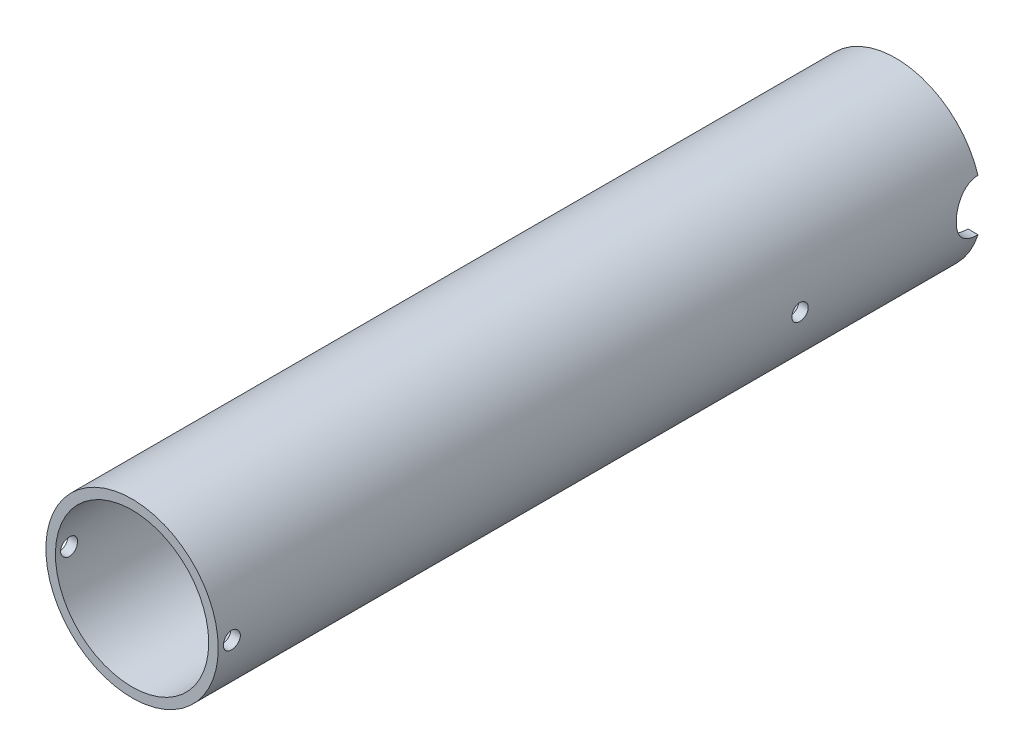
SolidWorks part; units mm, degrees
ref_plane "Front" through (0, 0, 0) normal (0, 0, 1) x (1, 0, 0)
ref_plane "Top" through (0, 0, 0) normal (0, 1, 0) x (1, 0, 0)
ref_plane "Right" through (0, 0, 0) normal (1, 0, 0) x (0, 0, -1)
sketch "Sketch1" plane through (0, 0, 0) normal (0, 0, 1) x (1, 0, 0)
  circle A0 centre (0, 0) radius 15.8
  circle A1 centre (0, 0) radius 14.05
extrude "Extrude1" add sketch "Sketch1" along normal blind 140
sketch "Sketch2" plane through (0, 0, 0) normal (1, 0, 0) x (0, 0, -1)
  line L0 (-140, 0) -> (0, 0) construction
  circle A0 centre (-137.5, 0) radius 1.55
  circle A1 centre (0, 0) radius 4.71
  circle A2 centre (-33.3375, 0) radius 1.5
extrude "Cut-Extrude1" cut sketch "Sketch2" against normal through all and the other way through all
